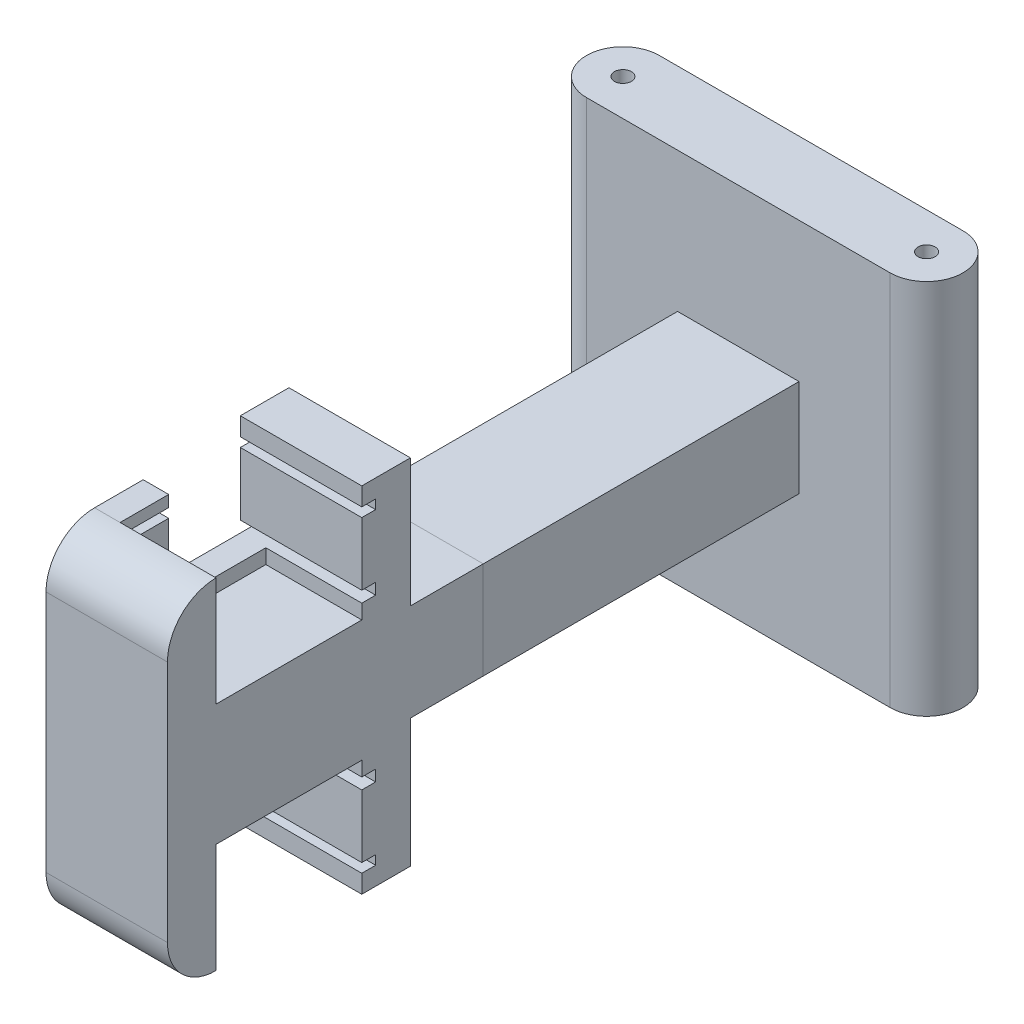
SolidWorks part; units mm, degrees
material "ABS"
ref_plane "Front Plane" through (0, 0, 0) normal (0, 0, 1) x (1, 0, 0)
ref_plane "Top Plane" through (0, 0, 0) normal (0, 1, 0) x (1, 0, 0)
ref_plane "Right Plane" through (0, 0, 0) normal (1, 0, 0) x (0, 0, -1)
sketch "Sketch1" plane through (0, 0, 0) normal (0, 1, 0) x (1, 0, 0)
  line L0 (-62.5, 15) -> (62.5, 15)
  line L1 (-62.5, -15) -> (62.5, -15) construction
  line L2 (-62.5, -15) -> (-62.5, 15) construction
  line L3 (-62.5, 15) -> (62.5, 15) construction
  line L4 (62.5, -15) -> (62.5, 15) construction
  line L5 (-62.5, -15) -> (62.5, 15) construction
  line L6 (-62.5, 15) -> (62.5, -15) construction
  line L7 (-62.5, -15) -> (62.5, -15)
  arc A0 (-62.5, 15) -> (-62.5, -15) centre (-62.5, 0) ccw
  arc A1 (62.5, -15) -> (62.5, 15) centre (62.5, 0) ccw
  circle A2 centre (-62.5, 0) radius 3.5
  circle A3 centre (62.5, 0) radius 3.5
  point P0 (0, 0)
  dimension "D1" = 125
  dimension "D2" = 30
  dimension "D4" = 7
  dimension "D3" = 30
extrude "Boss-Extrude1" add sketch "Sketch1" along normal mid plane 155
sketch "Sketch2" plane through (0, 0, 15) normal (0, 0, 1) x (1, 0, 0)
  line L1 (-25, 20) -> (25, 20)
  line L2 (-25, 20) -> (-25, -20)
  line L3 (-25, -20) -> (25, -20)
  line L4 (25, 20) -> (25, -20)
  line L5 (-25, 20) -> (25, -20) construction
  line L6 (-25, -20) -> (25, 20) construction
  point P0 (0, 0)
  dimension "D1" = 50
  dimension "D2" = 40
extrude "Boss-Extrude2" add sketch "Sketch2" along normal blind 260
sketch "Sketch5" plane through (0, 0, 0) normal (1, 0, 0) x (0, 0, -1)
  line L0 (-275, -20) -> (-15, -20) construction
  line L1 (-275, -20) -> (-175, -20)
  line L2 (-175, -72.8) -> (-175, -20)
  line L5 (-255, -70) -> (-255, -25)
  line L6 (-255, -25) -> (-195, -25)
  line L7 (-195, -25) -> (-195, -31)
  line L8 (-195, -61.5) -> (-189.3, -61.5)
  line L9 (-195, -35.6) -> (-189.3, -35.6)
  line L10 (-189.3, -35.6) -> (-189.3, -31)
  line L11 (-189.3, -31) -> (-195, -31)
  line L12 (-195, -35.6) -> (-195, -61.5)
  line L13 (-275, 20) -> (-275, -20) construction
  line L14 (-275, -20) -> (-275, -50)
  line L16 (-175, -72.8) -> (-195, -72.8)
  line L17 (-195, -72.8) -> (-195, -65.3)
  line L18 (-195, -65.3) -> (-189.3, -65.3)
  line L19 (-189.3, -65.3) -> (-189.3, -61.5)
  arc A0 (-275, -50) -> (-255, -70) centre (-255, -50) ccw
  dimension "D1" = 20
  dimension "D2" = 5
  dimension "D3" = 7.5
  dimension "D4" = 5.7
  dimension "D5" = 5.7
  dimension "D6" = 34.3
  dimension "D7" = 45
  dimension "D8" = 3.8
  dimension "D9" = 4.6
  dimension "D10" = 6
  dimension "D12" = 20
  dimension "D13" = 20
  dimension "D14" = 60
extrude "Boss-Extrude4" add sketch "Sketch5" along normal up to surface and the other way up to surface up to face at (25, 0, 145) other way up to face at (-25, 0, 145)
sketch "Sketch6" plane through (-25, 0, 0) normal (-1, 0, 0) x (0, 0, 1)
  line L0 (195, -25) -> (255, -25) construction
  line L1 (255, -70) -> (235, -70)
  line L2 (255, -70) -> (255, -25)
  line L3 (255, -25) -> (235, -25)
  line L4 (235, -70) -> (235, -25)
  dimension "D1" = 20
extrude "Boss-Extrude5" add sketch "Sketch6" against normal blind 4.9
sketch "Sketch8" plane through (0, 0, 0) normal (1, 0, 0) x (0, 0, -1)
  line L1 (-260, 20) -> (-184.3, 20)
  line L2 (-260, 20) -> (-260, -10)
  line L3 (-255, -15) -> (-189.3, -15)
  line L4 (-184.3, 20) -> (-184.3, -10)
  line L7 (-195, -25) -> (-255, -25) construction
  line L12 (-275, 20) -> (-15, 20) construction
  line L13 (-189.3, -35.6) -> (-189.3, -31) construction
  line L14 (-255, -25) -> (-255, -70) construction
  arc A0 (-189.3, -15) -> (-184.3, -10) centre (-189.3, -10) ccw
  arc A1 (-260, -10) -> (-255, -15) centre (-255, -10) ccw
  dimension "D4" = 5
  dimension "D2" = 5
  dimension "D1" = 10
extrude "Cut-Extrude1" [suppressed] cut sketch "Sketch8" against normal up to surface (50 mm away) from surface
mirror "Mirror1" about plane through (0, 0, 0) normal (0, 1, 0) of "Cut-Extrude1", "Boss-Extrude5", "Boss-Extrude4"
sketch "Sketch9" plane through (-20.1, 0, 0) normal (1, 0, 0) x (0, 0, -1)
  line L0 (-255, -70) -> (-255, -25) construction
  line L1 (-235, -70) -> (-255, -70)
  line L2 (-235, -70) -> (-235, -65.3)
  line L3 (-235, -65.3) -> (-255, -65.3)
  line L4 (-255, -70) -> (-255, -65.3)
  line L5 (-255, -25) -> (-235, -25) construction
  line L6 (-255, -31) -> (-195, -31)
  line L7 (-255, -31) -> (-255, -25)
  line L8 (-255, -25) -> (-195, -25)
  line L9 (-195, -31) -> (-195, -25)
  line L10 (-195, -31) -> (-195, -25) construction
  line L11 (-235, -25) -> (-235, -70) construction
  line L12 (-235, -35.6) -> (-255, -35.6)
  line L13 (-235, -35.6) -> (-235, -61.5)
  line L14 (-235, -61.5) -> (-255, -61.5)
  line L15 (-255, -35.6) -> (-255, -61.5)
  line L16 (-189.3, -31) -> (-195, -31) construction
  line L17 (-195, -35.6) -> (-189.3, -35.6) construction
  line L18 (-189.3, -61.5) -> (-195, -61.5) construction
  line L19 (-195, -65.3) -> (-189.3, -65.3) construction
extrude "Boss-Extrude7" add sketch "Sketch9" along normal blind 5.6
sketch "Sketch11" plane through (-20.1, 0, 0) normal (-1, 0, 0) x (0, 0, 1)
  line L0 (235, -31) -> (195, -31) construction
  line L1 (235, -25) -> (195, -25)
  line L2 (235, -25) -> (235, -31)
  line L3 (235, -31) -> (195, -31)
  line L4 (195, -25) -> (195, -31)
  line L5 (195, -31) -> (195, -25) construction
extrude "Boss-Extrude8" add sketch "Sketch11" along normal up to surface (4.9 mm away) up to face at (-25, 0, 193.9025)
mirror "Mirror2" about plane through (0, 0, 0) normal (0, 1, 0) of "Boss-Extrude7", "Boss-Extrude8"
fillet "Fillet1" [suppressed] radius 40
fillet "Fillet2" [suppressed] radius 5
fillet "Fillet3" [suppressed] radius 40
fillet "Fillet4" [suppressed] radius 5
ref_plane "Split Plane" through (0, 0, 145) normal (0, 0, -1) x (-1, 0, 0)
split "Split1" trim tools "Split Plane" bodies to split 121 resulting bodies 116 117
equation "\"width\"=155"
equation "\"D1@Boss-Extrude1\"=\"width\""
